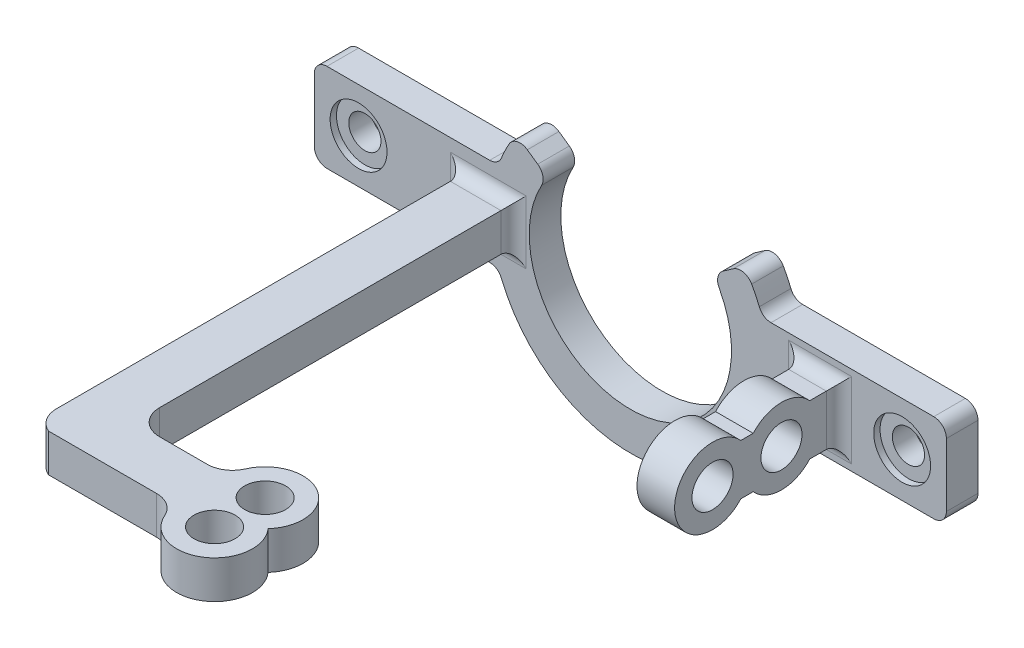
SolidWorks part; units mm, degrees
note: '?' marks a value the reader was unsure of.
ref_plane "Front Plane" through (0, 0, 0) normal (0, 0, 1) x (1, 0, 0)
ref_plane "Top Plane" through (0, 0, 0) normal (0, 1, 0) x (1, 0, 0)
ref_plane "Right Plane" through (0, 0, 0) normal (1, 0, 0) x (0, 0, -1)
sketch "Sketch1" plane through (0, 0, 0) normal (0, 0, 1) x (1, 0, 0)
  line L0 (100, 25) -> (100, 20)
  line L1 (100, 5) -> (100, 45) construction
  line L3 (98, 18) -> (72.2486, 18)
  line L4 (100, 25) -> (100, 30)
  line L5 (78.9438, 32) -> (98, 32)
  line L7 (78.9438, 32) -> (72.2486, 32)
  line L8 (54, 25) -> (106.793, 25) construction
  line L9 (50, 29) -> (50, 55.0668) construction
  line L16 (50, 25) -> (93.1322, 55.2015) construction
  line L17 (64.6534, 35.2604) -> (66.3009, 36.414)
  line L18 (50, 25) -> (6.8678, 55.2015) construction
  line L19 (46, 25) -> (-6.793, 25) construction
  line L20 (35.3466, 35.2604) -> (33.6991, 36.414)
  line L21 (21.0562, 32) -> (27.7514, 32)
  line L22 (2, 18) -> (27.7514, 18)
  line L23 (21.0562, 32) -> (2, 32)
  line L24 (0, 25) -> (0, 30)
  line L25 (0, 25) -> (0, 20)
  arc A0 (70.3945, 33.25) -> (69.1929, 35.7533) centre (50, 25) ccw
  arc A1 (35.955, 32.6641) -> (64.045, 32.6641) centre (50, 25) ccw
  arc A2 (29.6055, 16.75) -> (70.3945, 16.75) centre (50, 25) ccw
  circle A3 centre (93, 25) radius 2.55
  arc A14 (98, 32) -> (100, 30) centre (98, 30) cw
  arc A15 (98, 18) -> (100, 20) centre (98, 20) ccw
  arc A16 (72.2486, 18) -> (70.3945, 16.75) centre (72.2486, 16) ccw
  arc A17 (70.3945, 33.25) -> (72.2486, 32) centre (72.2486, 34) ccw
  arc A18 (64.6534, 35.2604) -> (64.045, 32.6641) centre (65.8006, 33.6221) ccw
  arc A19 (66.3009, 36.414) -> (69.1929, 35.7533) centre (67.4481, 34.7757) cw
  arc A21 (33.6991, 36.414) -> (30.8071, 35.7533) centre (32.5519, 34.7757) ccw
  arc A22 (35.3466, 35.2604) -> (35.955, 32.6641) centre (34.1994, 33.6221) cw
  arc A23 (29.6055, 33.25) -> (27.7514, 32) centre (27.7514, 34) cw
  arc A24 (27.7514, 18) -> (29.6055, 16.75) centre (27.7514, 16) cw
  arc A25 (2, 18) -> (0, 20) centre (2, 20) cw
  arc A26 (2, 32) -> (0, 30) centre (2, 30) ccw
  circle A27 centre (7, 25) radius 2.55
  arc A29 (29.6055, 33.25) -> (30.8071, 35.7533) centre (50, 25) cw
  point P30 (50, 3)
  point P31 (63.1064, 34.1772)
  point P35 (68.0213, 37.6187)
  point P39 (100, 32)
  point P73 (0, 32)
  point P74 (31.9787, 37.6187)
  point P75 (36.8936, 34.1772)
  dimension "D2" = 22
  dimension "D4" = 16
  dimension "D9" = 2
  dimension "D8" = 2
  dimension "D11" = 5.1
  dimension "D1" = 14
  dimension "D3" = 7
  dimension "D10" = 35
extrude "Boss-Extrude1" add sketch "Sketch1" along normal blind 5
fillet "Fillet2" [suppressed] radius 1
sketch "Sketch4" plane through (0, 0, 5) normal (0, 0, 1) x (1, 0, 0)
  circle A0 centre (93, 25) radius 4.5
  circle A1 centre (7, 25) radius 4.5
  dimension "D1" = 9
  dimension "D2" = 9
extrude "Cut-Extrude2" cut sketch "Sketch4" against normal blind 1
ref_axis "Axis1" through (93, 25, 4) along (0, 0, -1)?
ref_axis "Axis2" through (50, 25, 5) along (0, 0, -1)?
ref_plane "Plane1" through (0, 25, 0) normal (0, -1, 0) x (-1, 0, 0)
sketch "Sketch6" plane through (0, 25, 0) normal (0, -1, 0) x (-1, 0, 0)
  line L0 (-72.2486, -5) -> (-98, -5) construction
  line L1 (-77.0523, -5) -> (-83, -5)
  line L4 (-83, -5) -> (-83, -25)
  line L5 (-77.0523, -5) -> (-77.0523, -25)
  line L6 (-83, -25) -> (-77.0523, -25)
  line L7 (-93, -4) -> (-93, 0) construction
  dimension "D1" = 10
  dimension "D2" = 0
extrude "Boss-Extrude2" add sketch "Sketch6" along normal blind 4 and the other way blind 4
ref_plane "Plane2" through (77.0523, 21, 5) normal (1, 0, 0) x (0, 0, -1)
sketch "Sketch11" plane through (0, 0, 0) normal (0, 0, -1) x (-1, 0, 0)
  circle A0 centre (-93, 25) radius 4.5
  circle A1 centre (-7, 25) radius 4.5
  dimension "D1" = 9
  dimension "D2" = 9
extrude "Cut-Extrude3" cut sketch "Sketch11" against normal blind 0.5
thread "Thread1" [suppressed] pitch 0.8 start angle 0, offset 0, length 0, pitch 0.8, diameter 5.1
ref_plane "Plane3" through (90.45, 25, 4) normal (0, -1, 0) x (-1, 0, 0)
sketch "Thread Profile1" plane through (90.45, 25, 4) normal (0, -1, 0) x (-1, 0, 0)
  line L0 (0, 0) -> (0, 0.8) construction
  line L11 (0, 0) -> (0, 0.7)
  line L12 (0, 0.7) -> (-0.433, 0.45)
  line L13 (-0.433, 0.45) -> (-0.433, 0.25)
  line L15 (-0.433, 0.25) -> (0, 0)
  line L17 (-0.433, 0.35) -> (0, 0.35) construction
  point P2 (0, 0)
  dimension "Pitch" = 0.8
  dimension "Profile_Angle" = 60
  dimension "Profile_Land" = 0.2
  dimension "Profile_Height" = 0.433
sketch "Sketch16" plane through (0, 25, 0) normal (0, -1, 0) x (-1, 0, 0)
  line L0 (-52.2201, -73) -> (-52.2201, -96.0835) construction
  line L2 (-31.526, -5) -> (-31.526, -48.8515)
  line L4 (-23.526, -5) -> (-23.526, -69.3208)
  line L12 (-31.526, -48.8515) -> (-31.526, -61)
  line L14 (-43.0549, -65) -> (-35.526, -65)
  line L15 (-43.0549, -73) -> (-25.9566, -73)
  line L16 (-31.526, -5) -> (-23.526, -5)
  line L17 (-52.2201, -65) -> (-52.2201, -104.3674) construction
  line L18 (-27.7514, -5) -> (-2, -5) construction
  line L19 (-56.6922, -69) -> (-17.2144, -69) construction
  arc A0 (-56.6922, -69) -> (-46.721, -75.4) centre (-52.2201, -73) ccw
  circle A1 centre (-52.2201, -73) radius 3.25
  arc A3 (-25.9566, -73) -> (-23.526, -69.3208) centre (-27.526, -69.3208) ccw
  circle A5 centre (-52.2201, -65) radius 3.25
  arc A8 (-56.6922, -69) -> (-46.721, -62.6) centre (-52.2201, -65) cw
  arc A9 (-31.526, -61) -> (-35.526, -65) centre (-35.526, -61) cw
  arc A10 (-46.721, -62.6) -> (-43.0549, -65) centre (-43.0549, -61) ccw
  arc A11 (-46.721, -75.4) -> (-43.0549, -73) centre (-43.0549, -77) cw
  dimension "D5" = 6.5
  dimension "D7" = 4
  dimension "D10" = 6.5
  dimension "D13" = 4
  dimension "D3" = 8
  dimension "D4" = 6
  dimension "D9" = 6
  dimension "D2" = 0
  dimension "D6" = 0
  dimension "D12" = 8
  dimension "D8" = 4
  dimension "D11" = 60
extrude "Boss-Extrude3" add sketch "Sketch16" along normal blind 3 and the other way blind 3
fillet "Fillet3" radius 2 8 edges at (83, 25, 5) (80.0262, 29, 5) (77.0523, 25, 5) (80.0262, 21, 5) (27.526, 22, 5) (31.526, 25, 5) (23.526, 25, 5) (27.526, 28, 5)
sketch "Sketch17" plane through (83, 0, 0) normal (1, 0, 0) x (0, 0, -1)
  line L0 (-25, 29) -> (-25, 21) construction
  arc A0 (-19.5472, 27.5034) -> (-19.5472, 22.4966) centre (-25, 25) ccw
  arc A2 (-19.5472, 22.4966) -> (-19.5472, 27.5034) centre (-14.0944, 25) ccw
  dimension "D1" = 12
  dimension "D2" = 12
extrude "Boss-Extrude4" add sketch "Sketch17" against normal up to surface (5.9477 mm away) up to face at (77.0523, 25, 16)
sketch "Sketch18" plane through (83, 0, 0) normal (1, 0, 0) x (0, 0, -1)
  circle A0 centre (-25, 25) radius 3.25
  circle A1 centre (-14.0944, 25) radius 3.25
  dimension "D1" = 6.5
  dimension "D2" = 6.5
extrude "Cut-Extrude5" cut sketch "Sketch18" against normal up to next
thread "Thread2" [suppressed] pitch 0.8 start angle 0, offset 0, length 0, pitch 0.8, diameter 5.1
ref_plane "Plane4" through (4.45, 25, 4) normal (0, -1, 0) x (-1, 0, 0)
sketch "Thread Profile2" plane through (4.45, 25, 4) normal (0, -1, 0) x (-1, 0, 0)
  line L0 (0, 0) -> (0, 0.8) construction
  line L11 (0, 0) -> (0, 0.7)
  line L12 (0, 0.7) -> (-0.433, 0.45)
  line L13 (-0.433, 0.45) -> (-0.433, 0.25)
  line L15 (-0.433, 0.25) -> (0, 0)
  line L17 (-0.433, 0.35) -> (0, 0.35) construction
  point P2 (0, 0)
  dimension "Pitch" = 0.8
  dimension "Profile_Angle" = 60
  dimension "Profile_Land" = 0.2
  dimension "Profile_Height" = 0.433
equation "\"D3@Sketch1\"=\"D1@Sketch1\"/2"
equation "\"D8@Sketch16\"=\"D12@Sketch16\"/2"
